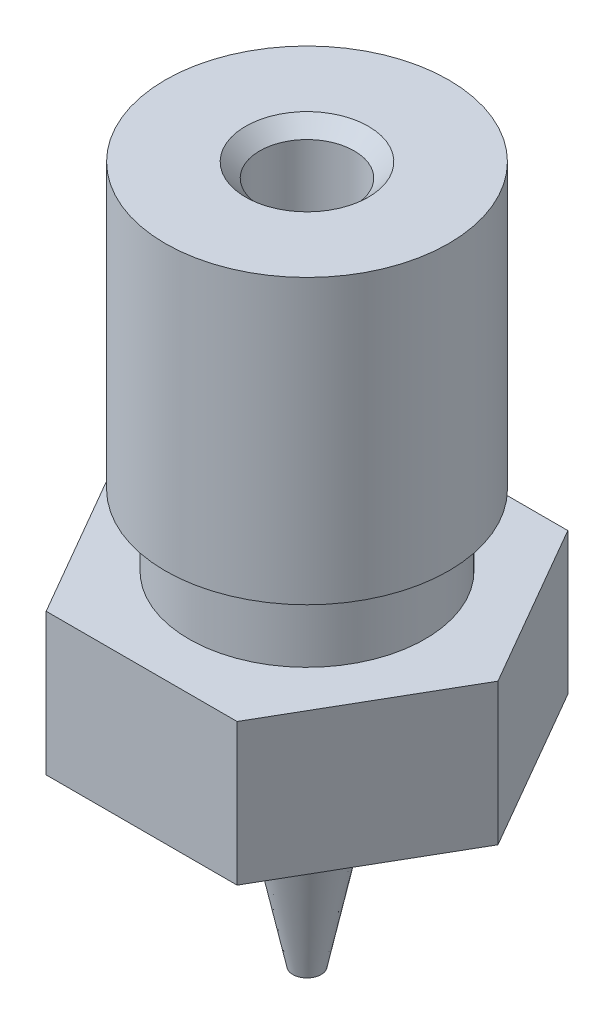
SolidWorks part; units mm, degrees
material "Brass"
ref_plane "Front Plane" through (0, 0, 0) normal (0, 0, 1) x (1, 0, 0)
ref_plane "Top Plane" through (0, 0, 0) normal (0, 1, 0) x (1, 0, 0)
ref_plane "Right Plane" through (0, 0, 0) normal (1, 0, 0) x (0, 0, -1)
sketch "Sketch1" plane through (0, 0, 0) normal (0, 0, 1) x (1, 0, 0)
  line L0 (0, 0) -> (0.5, 0)
  line L1 (0.5, 0) -> (1.9004, 2)
  line L2 (1.9004, 2) -> (3.5, 2)
  line L3 (3.5, 2) -> (3.5, 5)
  line L4 (3.5, 5) -> (2.5, 5)
  line L5 (2.5, 5) -> (2.5, 6.5)
  line L6 (2.5, 6.5) -> (3, 6.5)
  line L7 (3, 6.5) -> (3, 12.5)
  line L8 (3, 12.5) -> (0, 12.5)
  line L9 (0, 12.5) -> (0, 0)
  line L11 (0, -1.1291) -> (0, -50001.1291) construction
  dimension "D1" = 125
  dimension "D2" = 1
  dimension "D3" = 7
  dimension "D4" = 5
  dimension "D5" = 6
  dimension "D6" = 6
  dimension "D7" = 7.5
  dimension "D8" = 10.5
  dimension "D9" = 12.5
revolve "Revolve1" add sketch "Sketch1" angle 360 about L11
sketch "Sketch2" plane through (0, 0, 0) normal (0, 0, 1) x (1, 0, 0)
  line L0 (0, 0) -> (0, 12.5) construction
  line L1 (3, 12.5) -> (-3, 12.5) construction
  line L2 (0, 12.5) -> (1.3, 12.5)
  line L3 (1, 12.2) -> (1, 1.9856)
  line L4 (1, 1.9856) -> (0.2, 0.6)
  line L5 (0.2, 0.6) -> (0.2, 0)
  line L6 (-0.5, 0) -> (0.5, 0) construction
  line L7 (0.2, 0) -> (0, 0)
  line L8 (0, 0) -> (0, 12.5)
  line L9 (1, 12.2) -> (1.3, 12.5)
  dimension "D1" = 0.4
  dimension "D2" = 2
  dimension "D3" = 1.3
  dimension "D4" = 30
  dimension "D5" = 0.6
  dimension "D6" = 45
revolve "Cut-Revolve1" cut sketch "Sketch2" angle 360 about L0
sketch "Sketch3" plane through (0, 2, 0) normal (0, -1, 0) x (1, 0, 0)
  line L1 (4.0415, 0) -> (2.0207, 3.5)
  line L2 (2.0207, 3.5) -> (-2.0207, 3.5)
  line L3 (-2.0207, 3.5) -> (-4.0415, 0)
  line L4 (-4.0415, 0) -> (-2.0207, -3.5)
  line L5 (-2.0207, -3.5) -> (2.0207, -3.5)
  line L6 (2.0207, -3.5) -> (4.0415, 0)
  circle A0 centre (0, 0) radius 3.5 construction
  circle A1 centre (0, 0) radius 3.5
  circle A2 centre (0, 0) radius 3.5
  circle M3 centre (0, 0) radius 3.5
  dimension "D1" = 0
extrude "Boss-Extrude1" add sketch "Sketch3" against normal blind 3 contours L3 L4 M3 | L2 L3 M3 | L1 L2 M3 | L5 L6 M3 | L4 L5 M3 | L6 L1 M3 region at (3.6175, 2, 0) region at (1.8087, 2, 3.1328) region at (1.8087, 2, -3.1328) region at (-1.8087, 2, 3.1328) region at (-1.8087, 2, -3.1328) region at (-3.6175, 2, 0)
sketch "Sketch4" plane through (0, 0, 0) normal (0, 0, 1) x (1, 0, 0)
  line L0 (0, 2) -> (0, -2.25) construction
  line L1 (2.0207, 2) -> (-2.0207, 2) construction
  line L2 (0, -2.25) -> (0.3, -2.25)
  line L3 (0.3, -2.25) -> (0.8851, 0.55)
  line L4 (1.3, 2) -> (0, 2)
  line L5 (0.8851, 0.55) -> (1.3, 0.55)
  line L6 (1.3, 0.55) -> (1.3, 2)
  line L7 (0.5, 0) -> (1.9004, 2) construction
  line L8 (0, 2) -> (0, -2.25)
  point P7 (1.4158, 0.5623)
  point P10 (0.8851, 0.55)
  dimension "D1" = 0.6
  dimension "D2" = 4.25
  dimension "D3" = 2.6
  dimension "D4" = 1.45
revolve "Revolve2" add sketch "Sketch4" angle 360 about L0
